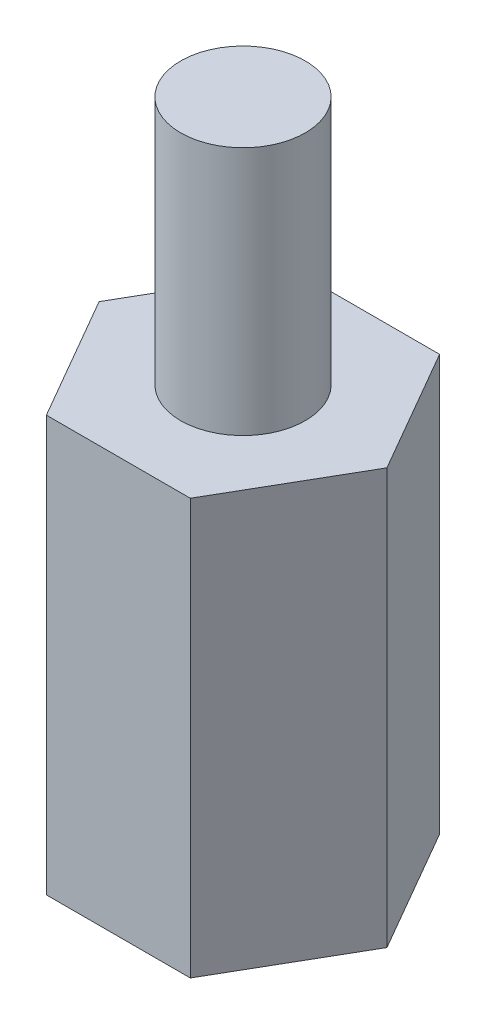
SolidWorks part; units mm, degrees
ref_plane "Front Plane" through (0, 0, 0) normal (0, 0, 1) x (1, 0, 0)
ref_plane "Top Plane" through (0, 0, 0) normal (0, 1, 0) x (1, 0, 0)
ref_plane "Right Plane" through (0, 0, 0) normal (1, 0, 0) x (0, 0, -1)
sketch "Sketch1" plane through (0, 0, 0) normal (0, 1, 0) x (1, 0, 0)
  line L1 (1.7321, -3) -> (3.4641, 0)
  line L2 (3.4641, 0) -> (1.7321, 3)
  line L3 (1.7321, 3) -> (-1.7321, 3)
  line L4 (-1.7321, 3) -> (-3.4641, 0)
  line L5 (-3.4641, 0) -> (-1.7321, -3)
  line L6 (-1.7321, -3) -> (1.7321, -3)
  circle A0 centre (0, 0) radius 3 construction
  dimension "D1" = 6
extrude "Boss-Extrude1" add sketch "Sketch1" along normal blind 10
sketch "Sketch2" plane through (0, 10, 0) normal (0, 1, 0) x (1, 0, 0)
  circle A0 centre (0, 0) radius 1.5
  dimension "D1" = 3
extrude "Boss-Extrude2" add sketch "Sketch2" along normal blind 6
extrude "Cut-Extrude1" cut sketch "Sketch2<2>" along normal blind 6 from surface starting at face at (0, 0, 0)
sketch "Sketch2<2>" plane through (0, 10, 0) normal (0, 1, 0) x (1, 0, 0) same geometry as "Sketch2"
